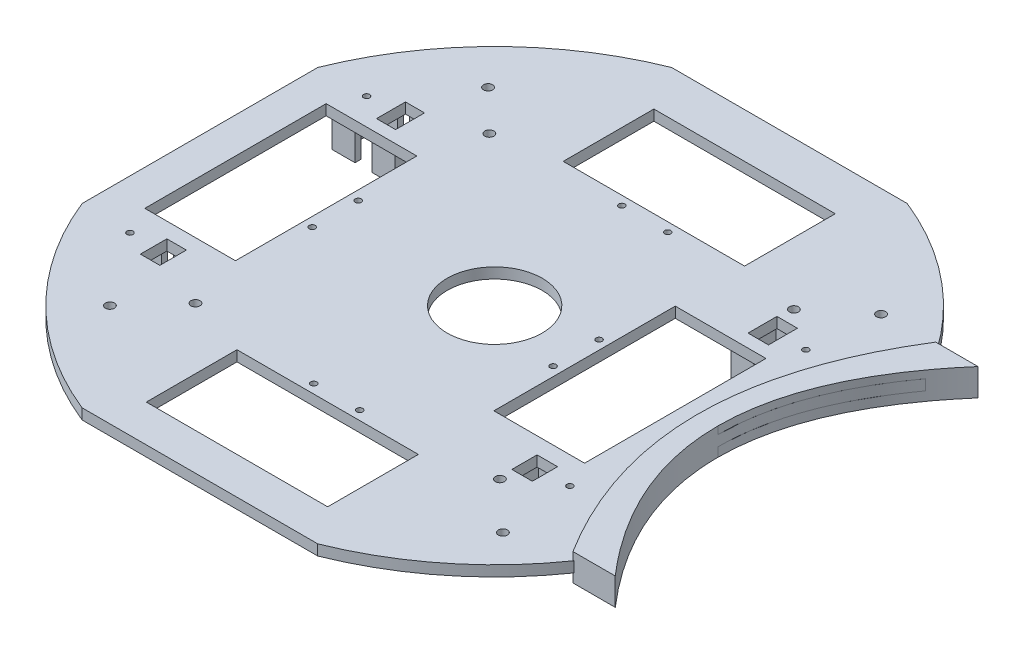
SolidWorks part; units mm, degrees
ref_plane "Front Plane" through (0, 0, 0) normal (0, 0, 1) x (1, 0, 0)
ref_plane "Top Plane" through (0, 0, 0) normal (0, 1, 0) x (1, 0, 0)
ref_plane "Right Plane" through (0, 0, 0) normal (1, 0, 0) x (0, 0, -1)
sketch "Sketch1" plane through (0, 0, 0) normal (0, 1, 0) x (1, 0, 0)
  line L1 (-97.5, -97.5) -> (97.5, -97.5)
  line L2 (-97.5, -97.5) -> (-97.5, 97.5)
  line L3 (-97.5, 97.5) -> (97.5, 97.5)
  line L4 (97.5, -97.5) -> (97.5, 97.5)
  line L5 (-97.5, -97.5) -> (97.5, 97.5) construction
  line L6 (-97.5, 97.5) -> (97.5, -97.5) construction
  point P0 (0, 0)
  dimension "D1" = 195
  dimension "D2" = 195
sketch "Sketch2" plane through (0, 0, 0) normal (0, 1, 0) x (1, 0, 0)
  line L0 (-97.5, -97.5) -> (97.5, 97.5) construction
  circle A0 centre (0, 0) radius 105
  circle A1 centre (0, 0) radius 177.8364
  dimension "D1" = 210
extrude "Boss-Extrude3" add sketch "Sketch1" along normal blind 3.5
extrude "Cut-Extrude2" cut sketch "Sketch2" along normal blind 30
sketch "Sketch4" plane through (0, 0, 0) normal (0, 1, 0) x (1, 0, 0)
  line L0 (30, -30.2592) -> (30, 29.7408)
  line L1 (0, 0) -> (0, -97.5) construction
  line L2 (30, -30.2592) -> (60, -30.2592)
  line L3 (0, 0) -> (0, 114.59) construction
  line L4 (-38.9711, -97.5) -> (38.9711, -97.5) construction
  line L5 (0, 0) -> (-44.5, 0) construction
  line L6 (-44.5, 0) -> (-97.5, 0) construction
  line L7 (-97.5, 38.9711) -> (-97.5, -38.9711) construction
  line L9 (-30, 52.6693) -> (30, 52.6693)
  line L10 (-30, 52.6693) -> (-30, 82.6693)
  line L11 (-30, 82.6693) -> (30, 82.6693)
  line L12 (30, 52.6693) -> (30, 82.6693)
  line L13 (-30, 52.6693) -> (30, 82.6693) construction
  line L14 (-30, 82.6693) -> (30, 52.6693) construction
  line L15 (-85.7442, -30) -> (-55.7442, -30)
  line L16 (-85.7442, -30) -> (-85.7442, 30)
  line L17 (-85.7442, 30) -> (-55.7442, 30)
  line L18 (-55.7442, -30) -> (-55.7442, 30)
  line L19 (-85.7442, -30) -> (-55.7442, 30) construction
  line L20 (-85.7442, 30) -> (-55.7442, -30) construction
  line L21 (-30, 52.6693) -> (-30, -55.2454) construction
  line L22 (-30, -85.2454) -> (30, -85.2454)
  line L23 (-30, -85.2454) -> (-30, -55.2454)
  line L24 (-30, -55.2454) -> (30, -55.2454)
  line L25 (30, -85.2454) -> (30, -55.2454)
  line L26 (-30, -85.2454) -> (30, -55.2454) construction
  line L27 (-30, -55.2454) -> (30, -85.2454) construction
  line L28 (-30, -55.2454) -> (-29.9439, -56.6452) construction
  line L29 (30, 52.6693) -> (30, -55.2454) construction
  line L30 (30, -55.2454) -> (30.8587, -54.4354) construction
  line L31 (-55.7442, -30) -> (85.9303, -30) construction
  line L32 (85.9303, -30) -> (85.9303, 30) construction
  line L33 (85.9303, 30) -> (-55.7442, 30) construction
  line L34 (30, 29.7408) -> (60, 29.7408)
  line L35 (60, -30.2592) -> (60, 29.7408)
  point P3 (-70.7442, 0)
  point P5 (0, 67.6693)
  point P6 (0, -70.2454)
  dimension "D2" = 30
  dimension "D3" = 30
  dimension "D4" = 60
  dimension "D5" = 60
  dimension "D6" = 30
  dimension "D7" = 53
  dimension "D8" = 90
  dimension "D9" = 30
  dimension "D10" = 60
  dimension "D11" = 60
extrude "Cut-Extrude7" cut sketch "Sketch4" along normal blind 5 contours L22 L25 L24 L23 | L2 L35 L34 L0 | L9 L12 L11 L10 | L15 L18 L17 L16 region at (45, 0, 0.2592) region at (0, 0, -67.6693) region at (-70.7442, 0, 0) region at (0, 0, 70.2454)
sketch "Sketch6" plane through (0, 0, 0) normal (0, 1, 0) x (1, 0, 0)
  line L0 (97.5, 0) -> (97.5, -60) construction
  line L1 (97.5, -38.9711) -> (97.5, 38.9711) construction
  line L2 (99.8878, 60) -> (85.8878, 60)
  line L3 (97.5, 0) -> (97.5, 60) construction
  line L4 (97.5, 60) -> (99.8878, 60) construction
  line L5 (99.8878, 60) -> (99.8878, -60) construction
  line L6 (99.8878, -60) -> (97.5, -60) construction
  line L7 (99.8878, -60) -> (85.8878, -60)
  spline S0 degree 2 poles (99.8878, 60) (47.8636, 0) (99.8878, -60) knots 0 0 0 1 1 1
  spline S1 degree 2 poles (85.8878, 60) (48.4396, 0) (85.8878, -60) knots 0 0 0 1 1 1
  dimension "D1" = 60
  dimension "D2" = 60
  dimension "D3" = 14
  dimension "D4" = 14
extrude "Boss-Extrude5" add sketch "Sketch6" along normal blind 6 and the other way blind 3
sketch "Sketch11" plane through (0, 0, 0) normal (0, 1, 0) x (1, 0, 0)
  line L0 (97.5, 0) -> (97.5, -60) construction
  line L2 (99.8878, -60) -> (114.5775, -60)
  line L3 (97.5, 0) -> (97.5, 59.9868) construction
  line L4 (97.5, 59.9868) -> (99.8878, 59.9868) construction
  line L5 (99.8878, 59.9868) -> (99.8878, -60) construction
  line L6 (99.8878, -60) -> (97.5, -60) construction
  line L7 (114.5775, -60) -> (112.4692, 59.9868)
  line L8 (112.4692, 59.9868) -> (99.8878, 59.9868)
  spline S0 degree 2 poles (99.8878, 59.9868) (47.8636, -0.0045) (99.8878, -60) knots 0 0 0 1 1 1
  dimension "D1" = 60
extrude "Cut-Extrude12" cut sketch "Sketch11" against normal blind 6 and the other way blind 6
sketch "Sketch13" plane through (0, 0, 0) normal (0, 1, 0) x (1, 0, 0)
  line L0 (-63.643, 61.4638) -> (66.357, 61.4638) construction
  line L1 (-63.643, 61.4638) -> (-63.643, -63.6362) construction
  line L2 (-63.643, -63.6362) -> (66.357, -63.6362) construction
  line L3 (0, 0) -> (-63.643, -63.6362) construction
  circle A0 centre (-63.643, 61.4638) radius 1.5
  circle A1 centre (66.357, 61.4638) radius 1.5
  circle A2 centre (66.357, -63.6362) radius 1.5
  circle A3 centre (-63.643, -63.6362) radius 1.5
  circle A4 centre (0, 0) radius 15.7219
  dimension "D1" = 3
  dimension "D3" = 3
  dimension "D4" = 3
  dimension "D5" = 3
  dimension "D2" = 130
  dimension "D6" = 125.1
  dimension "D7" = 130
  dimension "D9" = 90
extrude "top to mid stand" cut sketch "Sketch13" along normal blind 6
sketch "Sketch14" plane through (0, 0, 0) normal (0, 1, 0) x (1, 0, 0)
  line L0 (-50.174, 48.4164) -> (50.5569, 48.4164) construction
  line L1 (-50.174, -48.8116) -> (50.5569, 48.4164) construction
  line L2 (-50.174, -48.8116) -> (-50.174, 48.4164) construction
  line L3 (-50.174, 48.4164) -> (50.5569, -48.8116) construction
  circle A0 centre (-50.174, 48.4164) radius 1.5
  circle A1 centre (50.5569, 48.4164) radius 1.5
  circle A2 centre (50.5569, -48.8116) radius 1.5
  circle A3 centre (-50.174, -48.8116) radius 1.5
  dimension "D1" = 3
  dimension "D3" = 3
  dimension "D4" = 3
  dimension "D5" = 3
  dimension "D2" = 140
extrude "mit to bot stand" cut sketch "Sketch14" along normal blind 6
sketch "Sketch15" plane through (0, 0, 0) normal (0, 1, 0) x (1, 0, 0)
  line L0 (30, -30.2592) -> (30, 29.7408) construction
  line L1 (0, 49.6693) -> (7.6, 49.6693) construction
  line L2 (-55.6707, 0) -> (-52.6716, -0.0757) construction
  line L3 (30, 0) -> (27, 0) construction
  line L4 (-52.6716, -0.0757) -> (-52.6716, 7.5243) construction
  line L5 (-52.6716, -0.0757) -> (-52.6716, -7.6757) construction
  line L6 (-52.6716, 7.5243) -> (27, 7.5243) construction
  line L7 (27, 7.5243) -> (27, -7.6757) construction
  line L8 (27, -7.6757) -> (-52.6716, -7.6757) construction
  line L9 (0, 52.6693) -> (0, 49.6693) construction
  line L10 (0, -55.2454) -> (0, -52.2454) construction
  line L11 (-30, -55.2454) -> (30, -55.2454) construction
  line L12 (-30, 52.6693) -> (30, 52.6693) construction
  line L13 (0, 49.6693) -> (-7.6, 49.6693) construction
  line L14 (-7.6, -52.2454) -> (7.6, -52.2454) construction
  circle A0 centre (-52.6716, 7.5243) radius 1
  circle A1 centre (-52.6716, -7.6757) radius 1
  circle A2 centre (27, 7.5243) radius 1
  circle A3 centre (27, -7.6757) radius 1
  circle A4 centre (-7.6, 49.6693) radius 1
  circle A5 centre (7.6, 49.6693) radius 1
  circle A6 centre (-7.6, -52.2454) radius 1
  circle A7 centre (7.6, -52.2454) radius 1
  dimension "D6" = 2
  dimension "D7" = 2
  dimension "D8" = 2
  dimension "D9" = 2
  dimension "D14" = 2
  dimension "D15" = 2
  dimension "D16" = 2
  dimension "D17" = 2
  dimension "D1" = 3
  dimension "D2" = 3
  dimension "D3" = 90
  dimension "D4" = 7.6
  dimension "D5" = 7.6
  dimension "D10" = 3
  dimension "D11" = 3
  dimension "D12" = 7.6
  dimension "D13" = 7.6
extrude "Cut-Extrude13" cut sketch "Sketch15" along normal blind 10
sketch "Sketch16" plane through (0, 0, 0) normal (0, 1, 0) x (1, 0, 0)
  line L0 (-85.1282, 46.2544) -> (-85.1282, 31.3363)
  line L1 (-85.1282, 31.3363) -> (-77.531, 31.3363)
  line L2 (-77.531, 31.3363) -> (-77.531, 33.3363)
  line L3 (-77.531, 33.3363) -> (-83.231, 33.3363)
  line L4 (-83.231, 33.3363) -> (-83.231, 44.2544)
  line L5 (-83.231, 44.2544) -> (-76.4641, 44.2544)
  line L6 (-76.4641, 44.2544) -> (-76.4641, 46.2544)
  line L7 (-76.4641, 46.2544) -> (-85.1282, 46.2544)
  line L8 (-85.1282, 46.2544) -> (-76.4641, 46.2544)
  line L9 (-71.9499, 33.3544) -> (-71.9499, 31.3544)
  line L10 (-71.9499, 31.3544) -> (-64.3499, 31.3544)
  line L11 (-64.3499, 31.3544) -> (-64.3499, 46.2544)
  line L12 (-64.3499, 46.2544) -> (-72.4036, 46.2544)
  line L13 (-72.4036, 46.2544) -> (-72.4036, 44.2544)
  line L14 (-72.4036, 44.2544) -> (-66.2499, 44.2544)
  line L15 (-66.2499, 33.3544) -> (-66.2499, 44.2544)
  line L16 (-66.2499, 33.3544) -> (-71.9499, 33.3544)
  dimension "D1" = 7.5972
  dimension "D2" = 7.6
  dimension "D3" = 10.9181
  dimension "D4" = 10.9
  dimension "D5" = 2
  dimension "D6" = 2
  dimension "D7" = 2
  dimension "D8" = 2
  dimension "D9" = 5.7
  dimension "D10" = 5.7
sketch "Sketch17" plane through (0, 0, 0) normal (0, 1, 0) x (1, 0, 0)
  line L0 (46.8633, -32.1927) -> (46.8633, -47.1108)
  line L1 (46.8633, -47.1108) -> (54.4604, -47.1108)
  line L2 (54.4604, -47.1108) -> (54.4604, -45.1108)
  line L3 (54.4604, -45.1108) -> (48.7604, -45.1108)
  line L4 (48.7604, -45.1108) -> (48.7604, -34.1927)
  line L5 (48.7604, -34.1927) -> (55.498, -34.1927)
  line L6 (55.498, -34.1927) -> (55.498, -32.1927)
  line L7 (55.498, -32.1927) -> (46.8633, -32.1927)
  line L9 (60.5204, -45.0927) -> (60.5204, -47.0927)
  line L10 (60.5204, -47.0927) -> (68.1204, -47.0927)
  line L11 (68.1204, -47.0927) -> (68.1204, -32.1927)
  line L12 (68.1204, -32.1927) -> (59.9371, -32.1927)
  line L13 (59.9371, -32.1927) -> (59.9371, -34.1927)
  line L14 (59.9371, -34.1927) -> (66.2204, -34.1927)
  line L15 (66.2204, -34.1927) -> (66.2204, -45.0927)
  line L16 (66.2204, -45.0927) -> (60.5204, -45.0927)
  dimension "D1" = 7.5972
  dimension "D2" = 7.6
  dimension "D3" = 10.9181
  dimension "D4" = 10.9
  dimension "D5" = 2
  dimension "D6" = 2
  dimension "D7" = 2
  dimension "D8" = 2
  dimension "D9" = 5.7
  dimension "D10" = 5.7
sketch "Sketch18" plane through (0, 0, 0) normal (0, 1, 0) x (1, 0, 0)
  line L0 (46.8633, 46.2336) -> (46.8633, 31.3155)
  line L1 (46.8633, 31.3155) -> (54.4604, 31.3155)
  line L2 (54.4604, 31.3155) -> (54.4604, 33.3155)
  line L3 (54.4604, 33.3155) -> (48.7604, 33.3155)
  line L4 (48.7604, 33.3155) -> (48.7604, 44.2336)
  line L5 (48.7604, 44.2336) -> (55.498, 44.2336)
  line L6 (55.498, 44.2336) -> (55.498, 46.2336)
  line L7 (55.498, 46.2336) -> (46.8633, 46.2336)
  line L9 (60.5204, 33.3336) -> (60.5204, 31.3336)
  line L10 (60.5204, 31.3336) -> (68.1204, 31.3336)
  line L11 (68.1204, 31.3336) -> (68.1204, 46.2336)
  line L12 (68.1204, 46.2336) -> (59.9371, 46.2336)
  line L13 (59.9371, 46.2336) -> (59.9371, 44.2336)
  line L14 (59.9371, 44.2336) -> (66.2204, 44.2336)
  line L15 (66.2204, 44.2336) -> (66.2204, 33.3336)
  line L16 (66.2204, 33.3336) -> (60.5204, 33.3336)
  dimension "D1" = 7.5972
  dimension "D2" = 7.6
  dimension "D3" = 10.9181
  dimension "D4" = 10.9
  dimension "D5" = 2
  dimension "D6" = 2
  dimension "D7" = 2
  dimension "D8" = 2
  dimension "D9" = 5.7
  dimension "D10" = 5.7
sketch "Sketch20" plane through (0, 0, 0) normal (0, 1, 0) x (1, 0, 0)
  line L1 (-66.922, -35.0702) -> (-73.3624, -35.0702)
  line L2 (-66.922, -35.0702) -> (-66.922, -43.8394)
  line L3 (-66.922, -43.8394) -> (-73.3624, -43.8394)
  line L4 (-73.3624, -35.0702) -> (-73.3624, -43.8394)
  circle A0 centre (-81.1994, -39.4548) radius 1
  dimension "D1" = 2
extrude "Cut-Extrude14" cut sketch "Sketch20" along normal blind 10
sketch "Sketch22" plane through (0, 0, 0) normal (0, 1, 0) x (1, 0, 0)
  line L1 (-66.8183, 43.6097) -> (-73.1253, 43.6097)
  line L2 (-66.8183, 43.6097) -> (-66.8183, 34.0429)
  line L3 (-66.8183, 34.0429) -> (-73.1253, 34.0429)
  line L4 (-73.1253, 43.6097) -> (-73.1253, 34.0429)
  line L5 (56.5424, 43.6097) -> (49.7649, 43.6097)
  line L6 (56.5424, 43.6097) -> (56.5424, 34.0429)
  line L7 (56.5424, 34.0429) -> (49.7649, 34.0429)
  line L8 (49.7649, 43.6097) -> (49.7649, 34.0429)
  line L9 (56.5424, -35.7327) -> (49.7649, -35.7327)
  line L10 (56.5424, -35.7327) -> (56.5424, -44.0774)
  line L11 (56.5424, -44.0774) -> (49.7649, -44.0774)
  line L12 (49.7649, -35.7327) -> (49.7649, -44.0774)
  circle A0 centre (-81.1994, 38.8263) radius 1
  circle A1 centre (64.108, 38.8263) radius 1
  circle A2 centre (64.108, -39.2223) radius 1
  dimension "D1" = 2
  dimension "D2" = 2
  dimension "D3" = 2
extrude "Cut-Extrude15" cut sketch "Sketch22" along normal blind 10
extrude "Boss-Extrude6" add sketch "Sketch16" against normal blind 10 contours L6 L7 L0 L1 L2 L3 L4 L5 | L15 L16 L9 L10 L11 L12 L13 L14 region at (-80.7962, 0, -46.0819) region at (-69.0999, 0, -33.1851)
extrude "Boss-Extrude7" add sketch "Sketch18" against normal blind 10 contours L5 L6 L7 L0 L1 L2 L3 L4
extrude "Boss-Extrude8" add sketch "Sketch18<3>" against normal blind 10
sketch "Sketch18<3>" plane through (0, 0, 0) normal (0, 1, 0) x (1, 0, 0) same geometry as "Sketch18"
extrude "Boss-Extrude9" add sketch "Sketch17" against normal blind 10
sketch "Sketch23" plane through (0, 0, 0) normal (0, 1, 0) x (1, 0, 0)
  line L0 (-85.1282, -31.7687) -> (-85.1282, -46.6868)
  line L1 (-85.1282, -46.6868) -> (-77.531, -46.6868)
  line L2 (-77.531, -46.6868) -> (-77.531, -44.6868)
  line L3 (-77.531, -44.6868) -> (-83.231, -44.6868)
  line L4 (-83.231, -44.6868) -> (-83.231, -33.7687)
  line L5 (-83.231, -33.7687) -> (-76.4641, -33.7687)
  line L6 (-76.4641, -33.7687) -> (-76.4641, -31.7687)
  line L7 (-76.4641, -31.7687) -> (-85.1282, -31.7687)
  line L8 (-85.1282, -31.7687) -> (-76.4641, -31.7687)
  line L9 (-71.9499, -44.6687) -> (-71.9499, -46.6687)
  line L10 (-71.9499, -46.6687) -> (-64.3499, -46.6687)
  line L11 (-64.3499, -46.6687) -> (-64.3499, -31.7687)
  line L12 (-64.3499, -31.7687) -> (-72.4036, -31.7687)
  line L13 (-72.4036, -31.7687) -> (-72.4036, -33.7687)
  line L14 (-72.4036, -33.7687) -> (-66.2499, -33.7687)
  line L15 (-66.2499, -44.6687) -> (-66.2499, -33.7687)
  line L16 (-66.2499, -44.6687) -> (-71.9499, -44.6687)
  dimension "D1" = 7.5972
  dimension "D2" = 7.6
  dimension "D3" = 10.9181
  dimension "D4" = 10.9
  dimension "D5" = 2
  dimension "D6" = 2
  dimension "D7" = 2
  dimension "D8" = 2
  dimension "D9" = 5.7
  dimension "D10" = 5.7
extrude "Boss-Extrude10" add sketch "Sketch23" against normal blind 10 contours L6 L7 L0 L1 L2 L3 L4 L5 | L12 L13 L14 L15 L16 L9 L10 L11 region at (-80.7962, 0, 31.9412)
